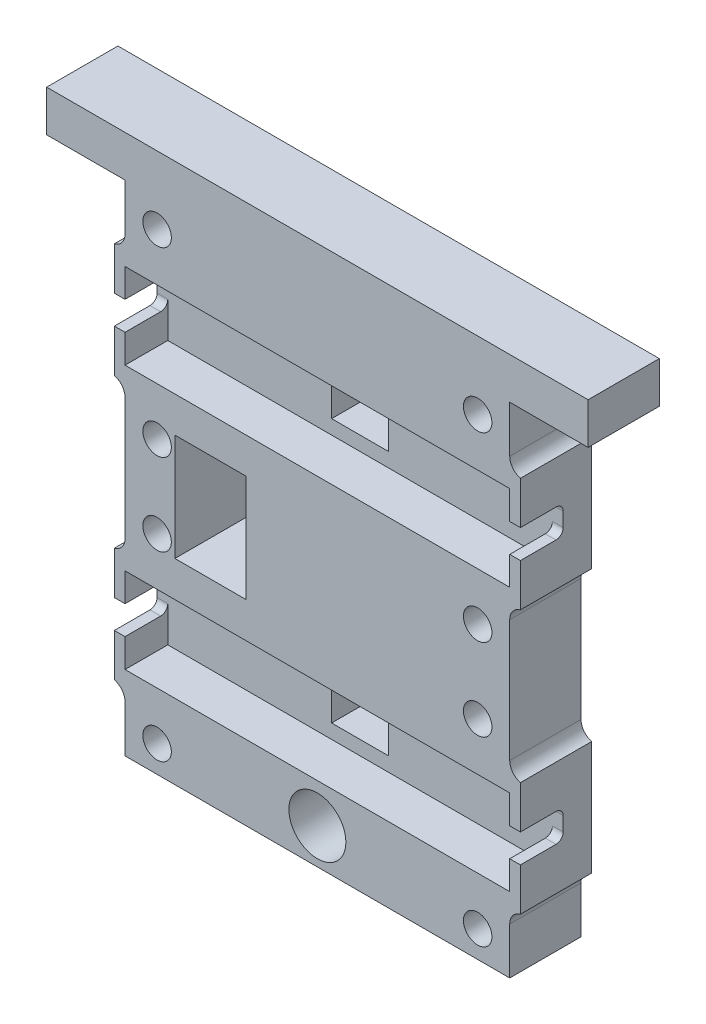
SolidWorks part; units mm, degrees
material "ABS"
ref_plane "Plano frontal" through (0, 0, 0) normal (0, 0, 1) x (1, 0, 0)
ref_plane "Plano superior" through (0, 0, 0) normal (0, 1, 0) x (1, 0, 0)
ref_plane "Plano direito" through (0, 0, 0) normal (1, 0, 0) x (0, 0, -1)
sketch "Esboço1" plane through (0, 0, 0) normal (0, 0, 1) x (1, 0, 0)
  line L0 (-22.1231, 28.35) -> (-22.1231, 2.85) construction
  line L2 (-26.6231, 32.1) -> (-26.6231, 23.6)
  line L3 (-26.6231, -37.9) -> (27.3769, -37.9)
  line L4 (27.3769, 32.1) -> (27.3769, 23.6)
  line L5 (-27.3795, 37.9037) -> (27.3769, -37.9) construction
  line L6 (-26.6231, -37.9) -> (26.6205, 37.8962) construction
  line L7 (-22.1231, 2.85) -> (22.8769, 2.85) construction
  line L8 (22.8769, -34.15) -> (22.8769, -8.65) construction
  line L9 (22.8769, -8.65) -> (-22.1231, -8.65) construction
  line L10 (0.3769, -37.9) -> (0.3769, 37.9) construction
  line L11 (27.3769, 32.1) -> (38.3769, 32.1)
  line L12 (38.3769, 32.1) -> (38.3769, 37.9)
  line L13 (-37.6231, 37.9) -> (38.3769, 37.9)
  line L14 (-37.6231, 37.9) -> (-37.6231, 32.1)
  line L15 (-37.6231, 32.1) -> (-26.6231, 32.1)
  line L33 (27.3769, -29.4) -> (27.3769, -37.9)
  line L35 (-26.6231, -37.9) -> (-26.6231, -29.4)
  line L38 (-28.1231, 15.6) -> (-26.6231, 15.6) construction
  line L39 (-26.6231, -13.4) -> (-28.1231, -13.4)
  line L41 (-26.6231, -29.4) -> (-28.1231, -29.4)
  line L42 (-28.1231, -13.4) -> (-28.1231, -29.4)
  line L43 (-26.6231, 23.6) -> (-28.1231, 23.6)
  line L45 (-26.6231, 7.6) -> (-28.1231, 7.6)
  line L46 (-28.1231, 23.6) -> (-28.1231, 7.6)
  line L47 (27.3769, -29.4) -> (28.8769, -29.4)
  line L48 (-28.1231, -21.4) -> (-26.6231, -21.4) construction
  line L49 (27.3769, -13.4) -> (28.8769, -13.4)
  line L50 (28.8769, -13.4) -> (28.8769, -29.4)
  line L51 (28.8769, 15.6) -> (27.3769, 15.6) construction
  line L52 (28.8769, 23.6) -> (28.8769, 7.6)
  line L53 (27.3769, 7.6) -> (28.8769, 7.6)
  line L54 (27.3769, 23.6) -> (28.8769, 23.6)
  line L55 (-26.6231, 7.6) -> (-26.6231, -13.4)
  line L56 (27.3769, -13.4) -> (27.3769, 7.6)
  circle A0 centre (-22.1231, 28.35) radius 2
  circle A1 centre (22.8769, 28.35) radius 2
  circle A2 centre (22.8769, -34.15) radius 2
  circle A3 centre (-22.1231, -34.15) radius 2
  circle A4 centre (-22.1231, -8.65) radius 2
  circle A5 centre (22.8769, -8.65) radius 2
  circle A6 centre (-22.1231, 2.85) radius 2
  circle A7 centre (22.8769, 2.85) radius 2
  circle A8 centre (0.3769, -32.9) radius 4
  point P0 (0, 0)
  dimension "D7" = 3.75
  dimension "D8" = 4
  dimension "D11" = 3.75
  dimension "D12" = 4
  dimension "D13" = 4
  dimension "D14" = 4
  dimension "D17" = 4
  dimension "D18" = 4
  dimension "D19" = 4
  dimension "D20" = 4
  dimension "D22" = 8
  dimension "D1" = 54
  dimension "D2" = 75.8
  dimension "D3" = 25.5
  dimension "D4" = 4.5
  dimension "D5" = 11.5
  dimension "D6" = 4.5
  dimension "D9" = 4.5
  dimension "D10" = 4.5
  dimension "D15" = 25.5
  dimension "D16" = 25.5
  dimension "D21" = 5
  dimension "D23" = 45
  dimension "D24" = 38
  dimension "D25" = 38
  dimension "D26" = 5.8
  dimension "D27" = 5.8
  dimension "D28" = 70
  dimension "D29" = 1.5
  dimension "D30" = 1.5
  dimension "D31" = 16
  dimension "D32" = 16
  dimension "D33" = 16.5
  dimension "D34" = 53.5
extrude "Ressalto-extrusão1" add sketch "Esboço1" along normal blind 10
sketch "Esboço7" plane through (0, 0, 0) normal (0, 0, -1) x (-1, 0, 0)
  line L0 (-0.3769, -37.9) -> (-0.3769, 37.9) construction
  line L1 (26.6231, -37.9) -> (-27.3769, -37.9) construction
  line L2 (-38.3769, 37.9) -> (37.6231, 37.9) construction
  line L3 (26.6231, 7.6) -> (26.6231, -13.4) construction
  line L4 (9.6231, 4.6) -> (19.6231, 4.6)
  line L5 (28.6231, 15.6) -> (-29.3769, 15.6) construction
  line L6 (9.6231, 4.6) -> (9.6231, -10.4)
  line L7 (-4.3769, 19.6) -> (3.6231, 19.6)
  line L8 (9.6231, -10.4) -> (19.6231, -10.4)
  line L9 (28.6231, -21.4) -> (-29.3769, -21.4) construction
  line L10 (19.6231, 4.6) -> (19.6231, -10.4)
  line L11 (-4.3769, 19.6) -> (-4.3769, 11.6)
  line L12 (-4.3769, 11.6) -> (3.6231, 11.6)
  line L13 (3.6231, 19.6) -> (3.6231, 11.6)
  line L14 (-4.3769, 19.6) -> (3.6231, 11.6) construction
  line L15 (-4.3769, 11.6) -> (3.6231, 19.6) construction
  line L16 (-4.3769, -17.4) -> (3.6231, -17.4)
  line L17 (-4.3769, -17.4) -> (-4.3769, -25.4)
  line L18 (-4.3769, -25.4) -> (3.6231, -25.4)
  line L19 (3.6231, -17.4) -> (3.6231, -25.4)
  line L20 (-4.3769, -17.4) -> (3.6231, -25.4) construction
  line L21 (-4.3769, -25.4) -> (3.6231, -17.4) construction
  point P18 (-0.3769, 15.6)
  point P23 (-0.3769, -21.4)
  dimension "D1" = 8
  dimension "D2" = 8
  dimension "D3" = 8
  dimension "D4" = 8
  dimension "D5" = 7
  dimension "D6" = 15
  dimension "D7" = 42.5
  dimension "D8" = 10
extrude "Corte-extrusão1" cut sketch "Esboço7" against normal through all
sketch "Esboço9" plane through (0, 0, 10) normal (0, 0, 1) x (1, 0, 0)
  line L0 (29.3769, 15.6) -> (-28.6231, 15.6) construction
  line L1 (27.3769, 9.6) -> (-26.6231, 9.6)
  line L2 (27.3769, 9.6) -> (27.3769, 13.6)
  line L3 (27.3769, 21.6) -> (-26.6231, 21.6)
  line L4 (-26.6231, 9.6) -> (-26.6231, 13.6)
  line L5 (27.3769, -15.4) -> (-26.6231, -15.4)
  line L6 (27.3769, -15.4) -> (27.3769, -19.4)
  line L7 (27.3769, -27.4) -> (-26.6231, -27.4)
  line L8 (-26.6231, -15.4) -> (-26.6231, -19.4)
  line L11 (-26.6231, -23.4) -> (-26.6231, -27.4)
  line L13 (29.3769, -21.4) -> (-28.6231, -21.4) construction
  line L15 (27.3769, -19.4) -> (29.3769, -19.4)
  line L17 (27.3769, -23.4) -> (29.3769, -23.4)
  line L18 (29.3769, -19.4) -> (29.3769, -23.4)
  line L19 (-26.6231, -19.4) -> (-28.6231, -19.4)
  line L21 (-26.6231, -23.4) -> (-28.6231, -23.4)
  line L22 (-28.6231, -19.4) -> (-28.6231, -23.4)
  line L23 (-26.6231, 17.6) -> (-28.6231, 17.6)
  line L25 (-26.6231, 13.6) -> (-28.6231, 13.6)
  line L26 (-28.6231, 17.6) -> (-28.6231, 13.6)
  line L27 (27.3769, 17.6) -> (29.3769, 17.6)
  line L29 (27.3769, 13.6) -> (29.3769, 13.6)
  line L30 (29.3769, 17.6) -> (29.3769, 13.6)
  line L31 (27.3769, -23.4) -> (27.3769, -27.4)
  line L32 (27.3769, 17.6) -> (27.3769, 21.6)
  line L33 (-26.6231, 17.6) -> (-26.6231, 21.6)
  line L34 (-26.6231, -37.9) -> (27.3769, -37.9) construction
  dimension "D1" = 2
  dimension "D2" = 2
  dimension "D3" = 2
  dimension "D4" = 2
  dimension "D5" = 2
  dimension "D6" = 2
  dimension "D7" = 2
  dimension "D8" = 6
  dimension "2" = 2
  dimension "D9" = 6
  dimension "D10" = 16.5
  dimension "D11" = 53.5
  dimension "D12" = 6
  dimension "D13" = 6
extrude "Corte-extrusão7" cut sketch "Esboço9" against normal blind 6
fillet "Filete1" radius 1 8 edges at (-27.3731, -19.4, 4) (-27.3731, -23.4, 4) (-27.3731, 13.6, 4) (-27.3731, 17.6, 4) (28.1269, 13.6, 4) (28.1269, 17.6, 4) (28.1269, -19.4, 4) (28.1269, -23.4, 4)
fillet "Filete2" radius 2 8 edges at (-26.6231, 23.6, 5) (27.3769, 23.6, 5) (27.3769, 7.6, 5) (27.3769, -13.4, 5) (27.3769, -29.4, 5) (-26.6231, -29.4, 5) (-26.6231, -13.4, 5) (-26.6231, 7.6, 5)
